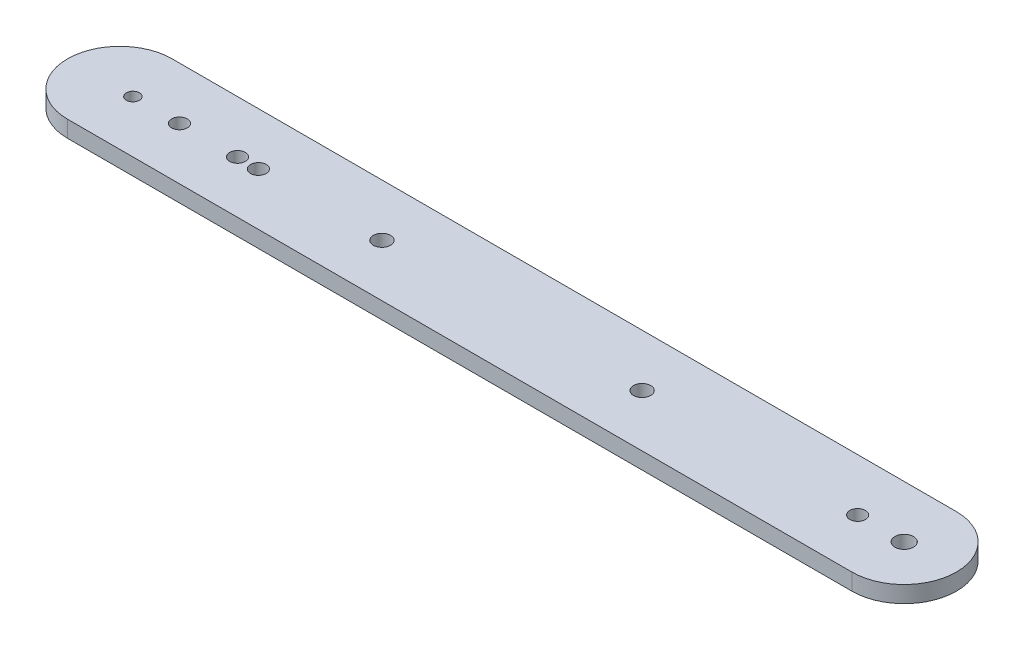
SolidWorks part; units mm, degrees
ref_plane "Front Plane" through (0, 0, 0) normal (0, 0, 1) x (1, 0, 0)
ref_plane "Top Plane" through (0, 0, 0) normal (0, 1, 0) x (1, 0, 0)
ref_plane "Right Plane" through (0, 0, 0) normal (1, 0, 0) x (0, 0, -1)
sketch "Sketch1" plane through (0, 0, 0) normal (0, 1, 0) x (1, 0, 0)
  line L0 (-85, -2.5) -> (85, -2.5) construction
  line L1 (-75, 7.5) -> (75, 7.5)
  line L3 (-75, -12.5) -> (75, -12.5)
  line L7 (0, 7.5) -> (0, -12.5) construction
  arc A0 (-75, 7.5) -> (-75, -12.5) centre (-75, -2.5) ccw
  arc A1 (75, -12.5) -> (75, 7.5) centre (75, -2.5) ccw
  circle A7 centre (-63.6, -2.5) radius 1.5
  circle A8 centre (-52.5, -2.5) radius 1.5
  circle A10 centre (-48.5, -2.5) radius 1.5
  circle A11 centre (66.1, -2.5) radius 1.5
  circle A12 centre (75, -2.5) radius 1.7758
  circle A13 centre (24.8747, -2.5) radius 1.65
  circle A14 centre (-24.8747, -2.5) radius 1.65
  circle A15 centre (-72.5, -2.5) radius 1.25
  point P0 (0, 0)
  point P30 (74.3679, -2.874)
  dimension "D6" = 3
  dimension "D9" = 3.3
  dimension "D7" = 2.5
  dimension "D2" = 11.1
  dimension "D3" = 4
  dimension "D4" = 20
  dimension "D5" = 150
  dimension "D8" = 8.9
  dimension "D10" = 25
  dimension "D11" = 8.9
  dimension "D12" = 0
extrude "Boss-Extrude1" add sketch "Sketch1" along normal blind 3.175
